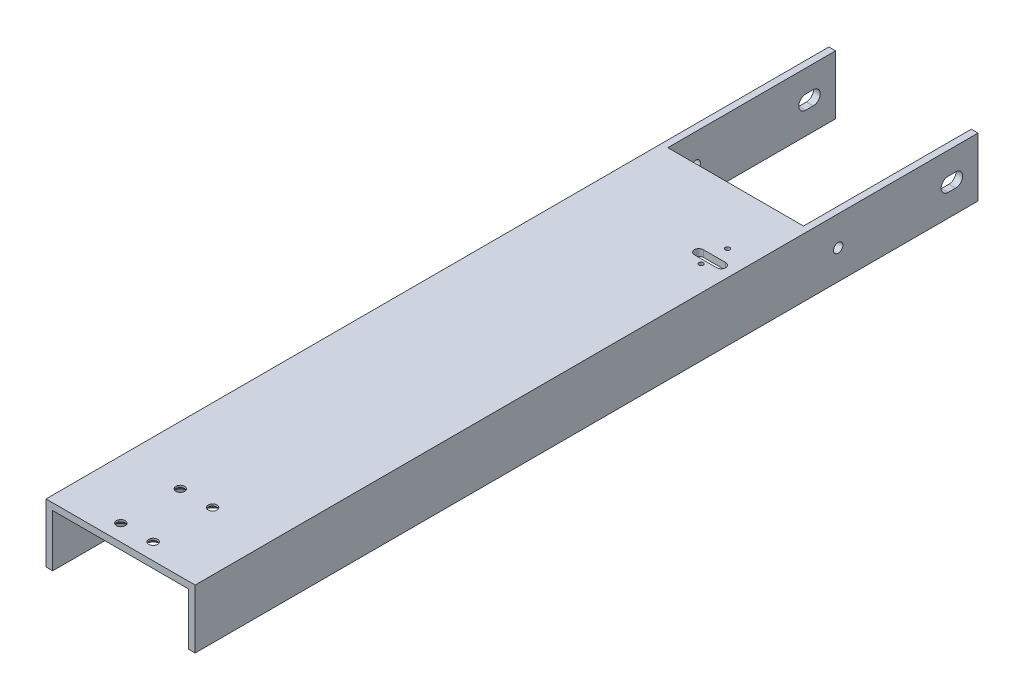
SolidWorks part; units mm, degrees
ref_plane "Front Plane" through (0, 0, 0) normal (0, 0, 1) x (1, 0, 0)
ref_plane "Top Plane" through (0, 0, 0) normal (0, 1, 0) x (1, 0, 0)
ref_plane "Right Plane" through (0, 0, 0) normal (1, 0, 0) x (0, 0, -1)
sketch "Sketch1" plane through (0, 0, 0) normal (0, 0, 1) x (1, 0, 0)
  line L0 (-50.8, 0) -> (50.8, 0)
  line L1 (50.8, 0) -> (50.8, -40.132)
  line L2 (50.8, -40.132) -> (46.228, -40.132)
  line L3 (46.228, -40.132) -> (46.228, -4.572)
  line L4 (46.228, -4.572) -> (-46.228, -4.572)
  line L5 (-46.228, -4.572) -> (-46.228, -40.132)
  line L6 (-46.228, -40.132) -> (-50.8, -40.132)
  line L7 (-50.8, -40.132) -> (-50.8, 0)
  point P8 (0, 0)
  dimension "D1" = 40.132
  dimension "D2" = 4.572
  dimension "D3" = 4.572
  dimension "D4" = 101.6
extrude "Boss-Extrude1" add sketch "Sketch1" along normal blind 533.4
sketch "Sketch3" plane through (0, 0, 0) normal (0, 1, 0) x (1, 0, 0)
  line L0 (50.8, 0) -> (-50.8, 0) construction
  line L1 (-46.228, -114.3) -> (46.228, -114.3)
  line L2 (-46.228, -114.3) -> (-46.228, 0)
  line L3 (-46.228, 0) -> (46.228, 0)
  line L4 (46.228, -114.3) -> (46.228, 0)
  line L5 (-46.228, -114.3) -> (46.228, 0) construction
  line L6 (-46.228, 0) -> (46.228, -114.3) construction
  line L7 (-46.228, -533.4) -> (-46.228, 0) construction
  line L8 (46.228, -533.4) -> (46.228, 0) construction
  line L9 (26.035, -165.4336) -> (41.275, -165.4336) construction
  line L10 (26.035, -162.3856) -> (41.275, -162.3856)
  line L11 (26.035, -168.4816) -> (41.275, -168.4816)
  line L12 (0, -1000) -> (0, 49000) construction
  line L13 (50.8, -533.4) -> (-50.8, -533.4) construction
  line L15 (50.8, -533.4) -> (50.8, 0) construction
  line L16 (-45.847, -161.1156) -> (46.228, -161.1156) construction
  arc A0 (26.035, -162.3856) -> (26.035, -168.4816) centre (26.035, -165.4336) ccw
  arc A1 (41.275, -168.4816) -> (41.275, -162.3856) centre (41.275, -165.4336) ccw
  circle A2 centre (33.655, -153.4956) radius 1.524
  circle A3 centre (33.655, -171.5296) radius 1.524
  circle A4 centre (-11.0109, -522.1859) radius 3
  circle A5 centre (11.0109, -481.6729) radius 3
  circle A6 centre (-11.0109, -481.6729) radius 3
  circle A7 centre (11.0109, -522.1859) radius 3
  point P0 (0, -57.15)
  point P13 (33.655, -165.4336)
  dimension "D2" = 6.096
  dimension "D6" = 3.048
  dimension "D9" = 6
  dimension "D1" = 114.3
  dimension "D3" = 15.24
  dimension "D4" = 9.525
  dimension "D5" = 1.27
  dimension "D7" = 3.048
  dimension "D8" = 8.89
  dimension "D10" = 40.513
  dimension "D11" = 22.0218
  dimension "D12" = 11.2141
extrude "Cut-Extrude1" cut sketch "Sketch3" against normal through all
sketch "Sketch4" plane through (50.8, 0, 0) normal (1, 0, 0) x (0, 0, -1)
  line L0 (-15.24, -20.066) -> (-20.32, -20.066) construction
  line L1 (-15.24, -24.8285) -> (-20.32, -24.8285)
  line L2 (-15.24, -15.3035) -> (-20.32, -15.3035)
  line L3 (0, -40.132) -> (0, 0) construction
  arc A0 (-15.24, -24.8285) -> (-15.24, -15.3035) centre (-15.24, -20.066) ccw
  arc A1 (-20.32, -15.3035) -> (-20.32, -24.8285) centre (-20.32, -20.066) ccw
  circle A2 centre (-95.25, -20.066) radius 3.175
  point P3 (-17.78, -20.066)
  point P10 (0, -20.066)
  dimension "D3" = 9.525
  dimension "D5" = 6.35
  dimension "D1" = 5.08
  dimension "D2" = 15.24
  dimension "D4" = 95.25
extrude "Cut-Extrude2" cut sketch "Sketch4" against normal through all
chamfer "Chamfer1" distance 3.25 angle 45 4 edges at (8.0109, -4.572, 481.6729) (8.0109, -4.572, 522.1859) (-14.0109, -4.572, 522.1859) (-14.0109, -4.572, 481.6729)
